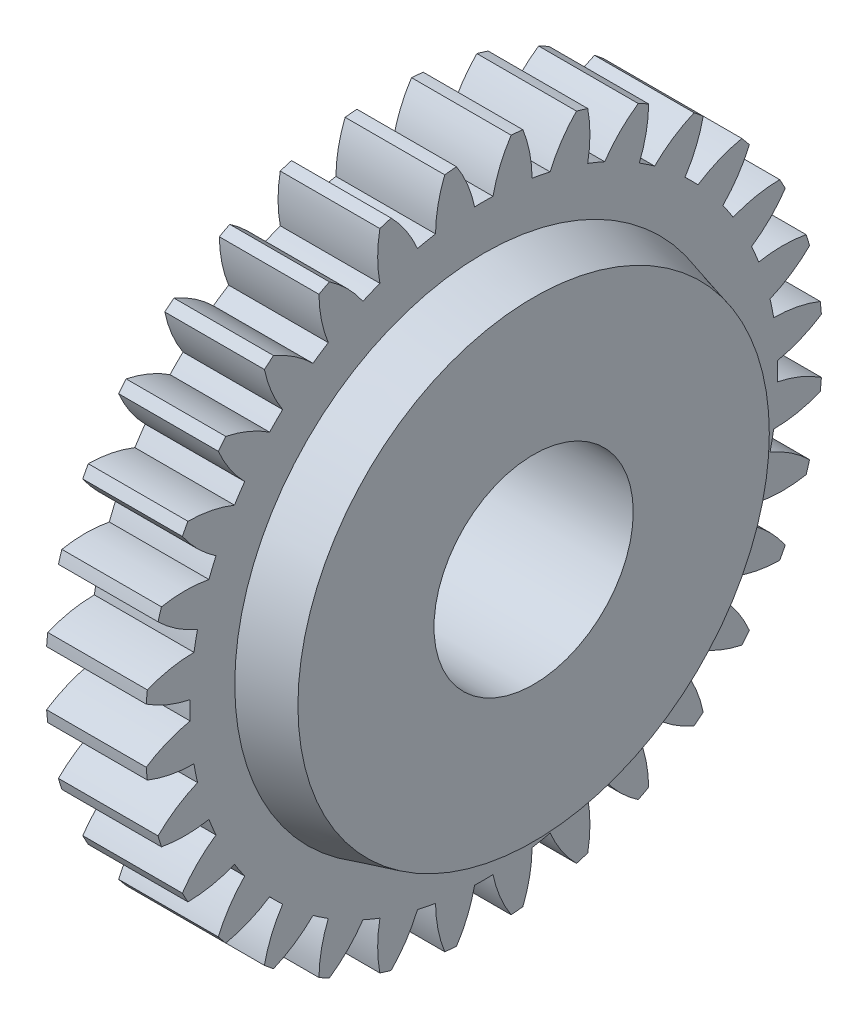
SolidWorks part; units mm, degrees
ref_plane "Plane1" through (0, 0, 0) normal (0, 0, 1) x (1, 0, 0)
ref_plane "Plane2" through (0, 0, 0) normal (0, 1, 0) x (1, 0, 0)
ref_plane "Plane3" through (0, 0, 0) normal (1, 0, 0) x (0, 0, -1)
sketch "HoldingSke" plane through (0, 0, 0) normal (0, 1, 0) x (1, 0, 0)
  line L0 (0, 0) -> (1.4134, -0.8832)
  line L1 (-15, 0) -> (100, 0) construction
  line L2 (0, 0) -> (-2.1039, 2.3779)
  line L3 (0, 0) -> (-11.863, 4.5341)
  line L4 (0, 0) -> (7.3237, 4.5764)
  line L5 (0, 0) -> (-46.8476, -17.4728)
  line L6 (0, 0) -> (-2.4869, -1.6779)
  line L7 (-2.1039, 2.3779) -> (8.6586, 51.2059)
  line L8 (-76.2, 54.61) -> (-75.2, 54.61)
  line L9 (-71.009, 38.7566) -> (-53.1078, 45.2721)
  line L10 (-76.2, 71.12) -> (104.1128, 71.12)
  line L11 (0, 0) -> (-3, 0)
  line L12 (-76.2, 101.6) -> (-76.177, 101.6)
  line L13 (24.9733, 27.94) -> (52.9518, 28.4284)
  line L14 (24.9733, 27.94) -> (24.9743, 27.94)
  line L15 (24.9733, 27.94) -> (100.4006, 29.5858)
  line L16 (-63.627, -0.6) -> (-12.827, -0.6)
  circle A0 centre (0, 0) radius 3
  circle A1 centre (0, 0) radius 8.849
  circle A2 centre (0, 0) radius 37.5
  circle A3 centre (0, 0) radius 3
  dimension "Num_teeth" = 32
  dimension "Pitch_radius" = 180.3128
  dimension "Width" = 3
  dimension "Thickness" = 3
sketch "BasProSke" plane through (0, 0, 0) normal (0, 1, 0) x (1, 0, 0)
  line L0 (-10, 0) -> (60, 0) construction
  line L1 (0, 0) -> (0, 10.2)
  line L2 (0, 0) -> (3, 0)
  line L3 (3, 0) -> (3, 10.2)
  line L4 (3, 10.2) -> (0, 10.2)
  dimension "Thickness" = 3
  dimension "Diameter" = 20.4
revolve "Base-Revolve" add sketch "BasProSke" angle 360 about L0
sketch "TooCutSke" plane through (0, 0, 0) normal (1, 0, 0) x (0, 0, -1)
  line L1 (0, 0) -> (0, 107) construction
  line L2 (0, 0) -> (-0.5113, 9.5864) construction
  line L3 (0, 0) -> (-1.88, 19.0883) construction
  line L4 (-0.5113, 9.5864) -> (-0.94, 9.5441) construction
  arc A0 (0.2775, 8.8446) -> (-0.2775, 8.8446) centre (0, 0) ccw
  arc A1 (0.8388, 10.1909) -> (-0.8388, 10.1909) centre (0, 0) ccw
  circle A2 centre (0, 0) radius 9.6 construction
  circle A3 centre (0, 0) radius 9.021 construction
  arc A4 (-0.2775, 8.8446) -> (-0.8388, 10.1909) centre (-4.0379, 8.0669) ccw
  arc A5 (0.8388, 10.1909) -> (0.2775, 8.8446) centre (4.0379, 8.0669) ccw
extrude "ToothCut" cut sketch "TooCutSke" along normal through all
fillet "Breaks" [suppressed] radius 0.012 tangent propagation no
fillet "RootFillets" [suppressed] radius 0.151
pattern_circular "TeethCuts" count 32 every 11.25 about axis through (-10, 0, 0) along (1, 0, 0) of "ToothCut", "RootFillets", "Breaks"
sketch "HubNeaOneSke" plane through (0, 0, 0) normal (-1, 0, 0) x (0, 0, 1)
  circle A0 centre (0, 0) radius 8.849
  dimension "Diameter" = 17.698
extrude "HubNearOne" [suppressed] add sketch "HubNeaOneSke" along normal blind 47.0001
sketch "HubNeaBotSke" plane through (0, 0, 0) normal (-1, 0, 0) x (0, 0, 1)
  circle A0 centre (0, 0) radius 8.849
  dimension "Diameter" = 17.698
extrude "HubNearBoth" [suppressed] add sketch "HubNeaBotSke" along normal blind 23.5
ref_plane "FarPln" through (3, 0, 0) normal (1, 0, 0) x (0, 0, -1)
sketch "Sketch1" plane through (3, 0, 0) normal (1, 0, 0) x (0, 0, -1)
  circle A0 centre (0, 0) radius 7.5
  dimension "D1" = 15
extrude "Boss-Extrude1" add sketch "Sketch1" along normal blind 1.5 draft 15
sketch "HubFarSke" plane through (3, 0, 0) normal (1, 0, 0) x (0, 0, -1)
  circle A0 centre (0, 0) radius 8.849
  dimension "Diameter" = 17.698
extrude "HubFar" [suppressed] add sketch "HubFarSke" along normal blind 23.5
sketch "BorSke" plane through (0, 0, 0) normal (1, 0, 0) x (0, 0, -1)
  circle A0 centre (0, 0) radius 3
  dimension "Diameter" = 6
extrude "Bore" cut sketch "BorSke" along normal mid plane 100.0001
sketch "KeySke" plane through (0, 0, 0) normal (1, 0, 0) x (0, 0, -1)
  line L0 (-1, 0) -> (-1, 4)
  line L1 (-1, 4) -> (1, 4)
  line L2 (1, 4) -> (1, 0)
  line L3 (0, 0) -> (0, 34) construction
  line L4 (-1, 0) -> (1, 0)
  dimension "Width" = 2
extrude "Keyway" [suppressed] cut sketch "KeySke" along normal mid plane 100.0001
pattern_circular "Keyway2" [suppressed] count 2 every 90 about axis through (-10, 0, 0) along (1, 0, 0)
equation "' \"Module@HoldingSke\" = 6.35"
equation "' \"Num_teeth@HoldingSke\" = 12"
equation "' \"Ap@HoldingSke\" =  20"
equation "' \"Ap@HoldingSke\" = 20"
equation "' \"Width@HoldingSke\" = 0.5 * 25.4"
equation "' \"Hub_dia@HoldingSke\"= 1 * 25.4"
equation "' \"Hub_dia@HoldingSke\" = 1 * 25.4"
equation "' \"Overall_len@HoldingSke\" = 1.0 * 25.4"
equation "' \"Bore@HoldingSke\" = 0.75 * 25.4"
equation "' \"T_dim@HoldingSke\" = 0.1 * 25.4"
equation "' \"Width@KeySke\" = 0.25 * 25.4"
equation "' \"Show_teeth@HoldingSke\" = 13"
equation "' \"Backlash@HoldingSke\" = 0.009 * 25.4"
equation "' \"Addendum_fac@HoldingSke\" = 1.0"
equation "' \"Dedendum_fac@HoldingSke\" = 1.25"
equation "' \"Dedendum_add@HoldingSke\" = 0.00005 * 25.4"
equation "' \"Clearance_fac@HoldingSke\" = 0.25"
equation "\"Pitch@HoldingSke\" = 1 / \"Module@HoldingSke\""
equation "\"Overcut_dia@TooCutSke\" = (\"Num_teeth@HoldingSke\" + 2 * \"Addendum_fac@HoldingSke\") / \"Pitch@HoldingSke\" + 0.002 * 25.4"
equation "\"Pitch_dia@TooCutSke\" = \"Num_teeth@HoldingSke\" / \"Pitch@HoldingSke\""
equation "\"Base_dia@TooCutSke\" = \"Num_teeth@HoldingSke\" / \"Pitch@HoldingSke\" * cos((\"Ap@HoldingSke\"  * 3.14159265 / 180))"
equation "\"Root_dia@TooCutSke\" = (\"Num_teeth@HoldingSke\" + 2) / \"Pitch@HoldingSke\" - 2 * (\"Addendum_fac@HoldingSke\" + \"Dedendum_fac@HoldingSke\") / \"Pitch@HoldingSke\" - \"Dedendum_add@HoldingSke\" * 2"
equation "\"Half_ang@TooCutSke\" = 180 / \"Num_teeth@HoldingSke\""
equation "\"Half_CT@TooCutSke\" = \"Num_teeth@HoldingSke\" / \"Pitch@HoldingSke\" * sin((3.14159265 / 2 / \"Num_teeth@HoldingSke\")) / 2 - 7 * \"Backlash@HoldingSke\" / 4"
equation "\"Flank_rad@TooCutSke\" = \"Num_teeth@HoldingSke\" / \"Pitch@HoldingSke\" / 5"
equation "\"Radius@RootFillets\" = \"Clearance_fac@HoldingSke\" / \"Pitch@HoldingSke\" + \"Dedendum_add@HoldingSke\""
equation "\"Break_rad@Breaks\" = 0.02 / \"Pitch@HoldingSke\""
equation "\"Thickness@HoldingSke\" = \"Width@HoldingSke\""
equation "\"OAL@HoldingSke\" = \"Thickness@HoldingSke\""
equation "\"MHD@HoldingSke\" = (\"Num_teeth@HoldingSke\" + 2) / \"Pitch@HoldingSke\" - 2 * (\"Addendum_fac@HoldingSke\" + \"Dedendum_fac@HoldingSke\")  / \"Pitch@HoldingSke\" - \"Dedendum_add@HoldingSke\" * 2"
equation "\"MBD@HoldingSke\" = (\"Num_teeth@HoldingSke\" + 2) / \"Pitch@HoldingSke\" - 2 * (\"Addendum_fac@HoldingSke\" + \"Dedendum_fac@HoldingSke\")  / \"Pitch@HoldingSke\" - \"Dedendum_add@HoldingSke\" * 2 - 0.002 * 25.4"
equation "\"MHD@HoldingSke\" = ((sgn( \"MHD@HoldingSke\" - \"Hub_dia@HoldingSke\" )-1)*( \"MHD@HoldingSke\" - \"Hub_dia@HoldingSke\" ))/-2+ \"Hub_dia@HoldingSke\""
equation "\"MBD@HoldingSke\" = ((sgn( \"MBD@HoldingSke\" - \"Bore@HoldingSke\" )-1)*( \"MBD@HoldingSke\" - \"Bore@HoldingSke\" ))/-2+ \"Bore@HoldingSke\""
equation "\"OAL@HoldingSke\" = ((sgn( \"OAL@HoldingSke\" - \"Overall_len@HoldingSke\" )+1)*( \"OAL@HoldingSke\" - \"Overall_len@HoldingSke\" ))/2 + \"Overall_len@HoldingSke\" + 0.000002 * 25.4"
equation "\"Num_teeth@TeethCuts\" = int( \"Show_teeth@HoldingSke\" ) + 1"
equation "\"Num_teeth@TeethCuts\" = ((sgn( \"Num_teeth@TeethCuts\" - \"Num_teeth@HoldingSke\" )-1)*( \"Num_teeth@TeethCuts\" - \"Num_teeth@HoldingSke\" ))/-2+ \"Num_teeth@HoldingSke\""
equation "\"Num_teeth@TeethCuts\" = ((sgn( \"Num_teeth@TeethCuts\" - 2.0)+1)*( \"Num_teeth@TeethCuts\" - 2.0))/2 +2.0"
equation "\"Angle@TeethCuts\" = 360.0 / \"Num_teeth@HoldingSke\""
equation "\"Diameter@BasProSke\" = (\"Num_teeth@HoldingSke\" + 2 * \"Addendum_fac@HoldingSke\") / \"Pitch@HoldingSke\""
equation "\"Thickness@BasProSke\"  = \"Thickness@HoldingSke\""
equation "' \"Fillet_rad@BasProSke\" =  \"Thickness@HoldingSke\" * 0.05"
equation "' \"Fillet_rad@BasProSke\" = \"Thickness@HoldingSke\" * 0.05"
equation "\"MHD@HoldingSke\" = ((sgn( \"MHD@HoldingSke\" - \"Root_dia@TooCutSke\" )-1)*( \"MHD@HoldingSke\" - \"Root_dia@TooCutSke\" ))/-2+ \"Root_dia@TooCutSke\""
equation "\"Diameter@HubNeaOneSke\" = \"MHD@HoldingSke\""
equation "\"Length@HubNearOne\" = \"OAL@HoldingSke\" - \"Thickness@BasProSke\""
equation "\"Diameter@HubNeaBotSke\" = \"MHD@HoldingSke\""
equation "\"Length@HubNearBoth\" = ( \"OAL@HoldingSke\" - \"Thickness@BasProSke\" ) / 2.0"
equation "\"Thickness@FarPln\" = \"Thickness@BasProSke\""
equation "\"Diameter@HubFarSke\" = \"MHD@HoldingSke\""
equation "\"Length@HubFar\" = ( \"OAL@HoldingSke\" - \"Thickness@BasProSke\" ) / 2.0"
equation "\"Diameter@BorSke\" = \"MBD@HoldingSke\""
equation "\"D1@Bore\" = \"OAL@HoldingSke\" * 2.0"
equation "\"D1@Keyway\" = \"OAL@HoldingSke\" * 2.0"
equation "\"Offset@KeySke\" = \"T_dim@HoldingSke\" + \"MBD@HoldingSke\" / 2.0"
